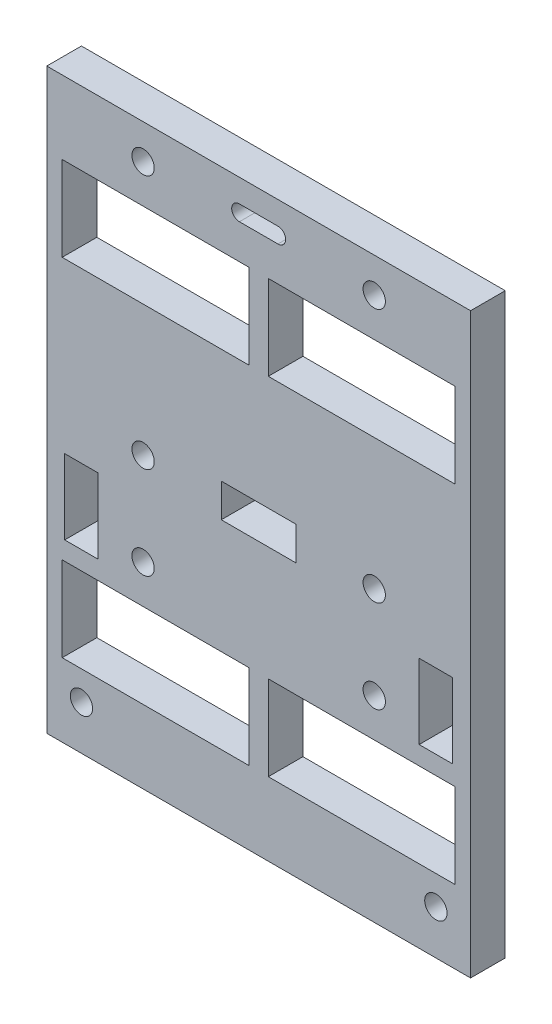
SolidWorks part; units mm, degrees
ref_plane "Front Plane" through (0, 0, 0) normal (0, 0, 1) x (1, 0, 0)
ref_plane "Top Plane" through (0, 0, 0) normal (0, 1, 0) x (1, 0, 0)
ref_plane "Right Plane" through (0, 0, 0) normal (1, 0, 0) x (0, 0, -1)
sketch "Sketch1" plane through (0, 0, 0) normal (0, 0, 1) x (1, 0, 0)
  line L0 (0, -37.5) -> (0, 37.5) construction
  line L1 (-27.5, -37.5) -> (27.5, -37.5)
  line L2 (-27.5, -37.5) -> (-27.5, 37.5)
  line L3 (-27.5, 37.5) -> (27.5, 37.5)
  line L4 (27.5, -37.5) -> (27.5, 37.5)
  line L5 (-27.5, -37.5) -> (27.5, 37.5) construction
  line L6 (-27.5, 37.5) -> (27.5, -37.5) construction
  line L7 (-27.5, 0) -> (27.5, 0) construction
  line L8 (-27.5, 22.5) -> (27.5, 22.5) construction
  line L9 (25.5, 17) -> (1.25, 28) construction
  line L10 (-25.5, 28) -> (-1.25, 28)
  line L11 (-25.5, 28) -> (-25.5, 17)
  line L12 (-25.5, 17) -> (-1.25, 17)
  line L13 (-1.25, 28) -> (-1.25, 17)
  line L14 (-25.5, 28) -> (-1.25, 17) construction
  line L15 (-25.5, 17) -> (-1.25, 28) construction
  line L16 (25.5, 28) -> (1.25, 17) construction
  line L17 (1.25, 28) -> (1.25, 17)
  line L18 (25.5, 17) -> (1.25, 17)
  line L19 (25.5, 28) -> (25.5, 17)
  line L20 (25.5, 28) -> (1.25, 28)
  line L21 (25.5, -28) -> (1.25, -17) construction
  line L22 (-25.5, -17) -> (-1.25, -28) construction
  line L23 (-25.5, -28) -> (-1.25, -17) construction
  line L24 (25.5, -17) -> (1.25, -28) construction
  line L25 (25.5, -28) -> (1.25, -28)
  line L26 (25.5, -28) -> (25.5, -17)
  line L27 (25.5, -17) -> (1.25, -17)
  line L28 (1.25, -28) -> (1.25, -17)
  line L29 (-1.25, -28) -> (-1.25, -17)
  line L30 (-25.5, -17) -> (-1.25, -17)
  line L31 (-25.5, -28) -> (-25.5, -17)
  line L32 (-25.5, -28) -> (-1.25, -28)
  point P0 (0, 0)
  point P12 (-13.375, 22.5)
  point P21 (13.375, 22.5)
  point P30 (13.375, -22.5)
  point P31 (-13.375, -22.5)
  dimension "D1" = 55
  dimension "D2" = 75
  dimension "D3" = 22.5
  dimension "D4" = 24.25
  dimension "D5" = 11
  dimension "D6" = 1.25
extrude "Boss-Extrude1" add sketch "Sketch1" along normal blind 4.5
sketch "Sketch2" plane through (0, 0, 4.5) normal (0, 0, 1) x (1, 0, 0)
  line L0 (0, -37.5) -> (0, 37.5) construction
  line L1 (-27.5, -37.5) -> (27.5, -37.5) construction
  line L2 (27.5, 37.5) -> (-27.5, 37.5) construction
  line L3 (-27.5, 0) -> (27.5, 0) construction
  line L4 (-27.5, 37.5) -> (-27.5, -37.5) construction
  line L5 (27.5, -37.5) -> (27.5, 37.5) construction
  line L6 (-15, 0) -> (15, 0) construction
  circle A0 centre (-15, 33) radius 1.45
  circle A1 centre (15, 33) radius 1.45
  circle A2 centre (15, 0) radius 1.45
  circle A3 centre (-15, 0) radius 1.45
  dimension "D1" = 2.9
  dimension "D7" = 2.9
  dimension "D8" = 2.9
  dimension "D2" = 15
  dimension "D3" = 33
  dimension "D4" = 30
  dimension "D5" = 15
  dimension "D6" = 0
extrude "screwHoles" cut sketch "Sketch2" against normal through all
sketch "Sketch3" plane through (0, 0, 4.5) normal (0, 0, 1) x (1, 0, 0)
  line L0 (-27.5, 9) -> (26.0486, 9) construction
  line L1 (-27.5, 37.5) -> (-27.5, -37.5) construction
  line L3 (0, 37.5) -> (0, -37.5) construction
  line L4 (27.5, 37.5) -> (-27.5, 37.5) construction
  line L5 (-27.5, -37.5) -> (27.5, -37.5) construction
  line L6 (18.95, 6.8) -> (9.05, 11.2) construction
  line L7 (-18.95, 11.2) -> (-9.05, 11.2)
  line L8 (-18.95, 11.2) -> (-18.95, 6.8)
  line L9 (-18.95, 6.8) -> (-9.05, 6.8)
  line L10 (-9.05, 11.2) -> (-9.05, 6.8)
  line L11 (-18.95, 11.2) -> (-9.05, 6.8) construction
  line L12 (-18.95, 6.8) -> (-9.05, 11.2) construction
  line L13 (18.95, 11.2) -> (9.05, 6.8) construction
  line L14 (9.05, 11.2) -> (9.05, 6.8)
  line L15 (18.95, 6.8) -> (9.05, 6.8)
  line L16 (18.95, 11.2) -> (18.95, 6.8)
  line L17 (18.95, 11.2) -> (9.05, 11.2)
  line L18 (-27.5, 37.5) -> (-27.5, -37.5) construction
  point P2 (-27.5, 0)
  point P12 (-14, 9)
  point P21 (14, 9)
  dimension "D1" = 9.9
  dimension "D3" = 14
  dimension "D4" = 9
extrude "BeltClamp" [suppressed] cut sketch "Sketch3" against normal through all
sketch "Sketch4" plane through (0, 0, 4.5) normal (0, 0, 1) x (1, 0, 0)
  line L0 (-27.5, 0) -> (27.5, 0) construction
  line L1 (-27.5, 37.5) -> (-27.5, -37.5) construction
  line L2 (27.5, -37.5) -> (27.5, 37.5) construction
  line L4 (-4.85, 2.175) -> (4.85, 2.175)
  line L5 (-4.85, 2.175) -> (-4.85, -2.175)
  line L6 (-4.85, -2.175) -> (4.85, -2.175)
  line L7 (4.85, 2.175) -> (4.85, -2.175)
  line L8 (-4.85, 2.175) -> (4.85, -2.175) construction
  line L9 (-4.85, -2.175) -> (4.85, 2.175) construction
  circle A0 centre (-15, 0) radius 1.45 construction
  point P6 (0, 0)
  dimension "D2" = 4.35
  dimension "D3" = 0
extrude "mountingPlateTab" cut sketch "Sketch4" against normal through all
sketch "Sketch5" plane through (0, 0, 4.5) normal (0, 0, 1) x (1, 0, 0)
  line L0 (-27.5, -9.75) -> (27.5, -9.75) construction
  line L1 (-27.5, 37.5) -> (-27.5, -37.5) construction
  line L2 (27.5, -37.5) -> (27.5, 37.5) construction
  line L4 (0, -37.5) -> (0, 37.5) construction
  line L5 (-27.5, -37.5) -> (27.5, -37.5) construction
  line L6 (27.5, 37.5) -> (-27.5, 37.5) construction
  line L7 (-20.825, -14.6) -> (-25.175, -4.9) construction
  line L8 (20.825, -4.9) -> (25.175, -4.9)
  line L9 (20.825, -4.9) -> (20.825, -14.6)
  line L10 (20.825, -14.6) -> (25.175, -14.6)
  line L11 (25.175, -4.9) -> (25.175, -14.6)
  line L12 (20.825, -4.9) -> (25.175, -14.6) construction
  line L13 (20.825, -14.6) -> (25.175, -4.9) construction
  line L14 (-20.825, -4.9) -> (-25.175, -14.6) construction
  line L15 (-25.175, -4.9) -> (-25.175, -14.6)
  line L16 (-20.825, -14.6) -> (-25.175, -14.6)
  line L17 (-20.825, -4.9) -> (-20.825, -14.6)
  line L18 (-20.825, -4.9) -> (-25.175, -4.9)
  line L19 (23, -9.75) -> (23, -37.5) construction
  line L20 (-23, -9.75) -> (-23, -37.5) construction
  circle A0 centre (23, -31.75) radius 1.45
  circle A1 centre (-23, -31.75) radius 1.45
  point P15 (23, -9.75)
  point P24 (-23, -9.75)
  dimension "D5" = 2.9
  dimension "D2" = 9.7
  dimension "D3" = 4.35
  dimension "D4" = 23
  dimension "D6" = 22
  dimension "D1" = 9.75
extrude "BraceTabs" cut sketch "Sketch5" against normal through all
sketch "Sketch6" plane through (0, 0, 4.5) normal (0, 0, 1) x (1, 0, 0)
  line L0 (-25.175, -9.75) -> (25.175, -9.75) construction
  line L1 (-25.175, -4.9) -> (-25.175, -14.6) construction
  line L2 (25.175, -14.6) -> (25.175, -4.9) construction
  line L3 (0, -2.175) -> (0, -37.5) construction
  line L4 (-4.85, -2.175) -> (4.85, -2.175) construction
  line L5 (-27.5, -37.5) -> (27.5, -37.5) construction
  line L6 (23, -14.6) -> (23, -4.9) construction
  line L7 (20.825, -14.6) -> (25.175, -14.6) construction
  line L8 (25.175, -4.9) -> (20.825, -4.9) construction
  line L9 (20.825, -4.9) -> (20.825, -14.6) construction
  line L10 (19.825, -15.6) -> (26.175, -15.6)
  line L11 (19.825, -15.6) -> (19.825, -3.9)
  line L12 (19.825, -3.9) -> (26.175, -3.9)
  line L13 (26.175, -15.6) -> (26.175, -3.9)
  line L14 (19.825, -15.6) -> (26.175, -3.9) construction
  line L15 (19.825, -3.9) -> (26.175, -15.6) construction
  line L16 (-19.825, -3.9) -> (-26.175, -15.6) construction
  line L17 (-19.825, -15.6) -> (-26.175, -3.9) construction
  line L18 (-23, -14.6) -> (-23, -4.9) construction
  line L19 (-26.175, -15.6) -> (-26.175, -3.9)
  line L20 (-19.825, -3.9) -> (-26.175, -3.9)
  line L21 (-19.825, -15.6) -> (-19.825, -3.9)
  line L22 (-19.825, -15.6) -> (-26.175, -15.6)
  circle A0 centre (23, -9.75) radius 1.45
  circle A1 centre (-23, -9.75) radius 1.45
  point P18 (23, -9.75)
  dimension "D3" = 2.9
  dimension "D1" = 1
  dimension "D2" = 1
extrude "FrontToRear1" [suppressed] add sketch "Sketch6" against normal up to surface (4.5 mm away) up to face at (-24.45, -31.75, 0)
sketch "Sketch7" plane through (0, 0, 4.5) normal (0, 0, 1) x (1, 0, 0)
  line L0 (4.85, 2.175) -> (-4.85, 2.175) construction
  line L1 (-20, -3.175) -> (20, -3.175)
  line L2 (-20, -3.175) -> (-20, 3.175)
  line L3 (-20, 3.175) -> (20, 3.175)
  line L4 (20, -3.175) -> (20, 3.175)
  line L5 (-20, -3.175) -> (20, 3.175) construction
  line L6 (-20, 3.175) -> (20, -3.175) construction
  circle A0 centre (15, 0) radius 1.45 construction
  point P0 (0, 0)
  dimension "D1" = 1
  dimension "D2" = 5
extrude "FrontToRear2" [suppressed] add sketch "Sketch7" against normal through all
sketch "Sketch8" plane through (0, 0, 4.5) normal (0, 0, 1) x (1, 0, 0)
  line L0 (-27.5, -12) -> (27.5, -12) construction
  line L1 (-27.5, 37.5) -> (-27.5, -37.5) construction
  line L2 (27.5, -37.5) -> (27.5, 37.5) construction
  line L3 (0, -37.5) -> (0, 0) construction
  line L4 (-27.5, -37.5) -> (27.5, -37.5) construction
  circle A0 centre (-15, -12) radius 1.45
  circle A1 centre (15, -12) radius 1.45
  dimension "D2" = 2.9
  dimension "D1" = 12
  dimension "D3" = 15
extrude "ExpansionScrewholes" cut sketch "Sketch8" against normal through all
sketch "Sketch12" plane through (0, 0, 4.5) normal (0, 0, 1) x (1, 0, 0)
  line L0 (0, 37.5) -> (0, 0) construction
  line L1 (27.5, 37.5) -> (-27.5, 37.5) construction
  line L2 (-2.5, 33.5) -> (2.5, 33.5) construction
  line L3 (-2.5, 34.5) -> (2.5, 34.5)
  line L4 (-2.5, 32.5) -> (2.5, 32.5)
  arc A0 (-2.5, 34.5) -> (-2.5, 32.5) centre (-2.5, 33.5) ccw
  arc A1 (2.5, 32.5) -> (2.5, 34.5) centre (2.5, 33.5) ccw
  point P7 (0, 33.5)
  dimension "D1" = 3
  dimension "D2" = 2
  dimension "D3" = 5
extrude "CableTieSlot" cut sketch "Sketch12" against normal through all
sketch "Sketch11" [suppressed] plane through (0, 0, 4.5) normal (0, 0, 1) x (1, 0, 0)
  line L0 (13.5615, -8.85) -> (27.5, -8.85) construction
  line L1 (27.5, -37.5) -> (27.5, 37.5) construction
  line L2 (0, 37.5) -> (0, -37.5) construction
  line L3 (36.5, -14.85) -> (18.5, -14.85)
  line L4 (36.5, -14.85) -> (36.5, -2.85)
  line L5 (36.5, -2.85) -> (18.5, -2.85)
  line L6 (18.5, -14.85) -> (18.5, -2.85)
  line L7 (36.5, -14.85) -> (18.5, -2.85) construction
  line L8 (36.5, -2.85) -> (18.5, -14.85) construction
  line L11 (-36.5, -2.85) -> (-18.5, -14.85) construction
  line L12 (-36.5, -14.85) -> (-18.5, -2.85) construction
  line L13 (-18.5, -14.85) -> (-18.5, -2.85)
  line L14 (-36.5, -2.85) -> (-18.5, -2.85)
  line L15 (-36.5, -14.85) -> (-36.5, -2.85)
  line L16 (-36.5, -14.85) -> (-18.5, -14.85)
  line L17 (36.5, -2.85) -> (18.5, -14.85) construction
  line L18 (20.65, -14.85) -> (25.35, -14.85) construction
  line L19 (27.5, 37.5) -> (-27.5, 37.5) construction
  line L20 (-27.5, -37.5) -> (27.5, -37.5) construction
  dimension "D1" = 9
  dimension "D2" = 12
  dimension "D3" = 0
extrude "Cut-Extrude2" [suppressed] cut sketch "Sketch11" against normal through all
sketch "Sketch10" plane through (0, 0, 4.5) normal (0, 0, 1) x (1, 0, 0)
  line L0 (4.7446, 1) -> (27.5, 1) construction
  line L1 (-4.85, 0) -> (4.85, 0) construction
  line L2 (27.5, -37.5) -> (27.5, 37.5) construction
  line L3 (0, 2.175) -> (0, -2.175) construction
  line L4 (36.5, 4) -> (18.5, 4)
  line L5 (36.5, 4) -> (36.5, -2)
  line L6 (36.5, -2) -> (18.5, -2)
  line L7 (18.5, 4) -> (18.5, -2)
  line L8 (36.5, 4) -> (18.5, -2) construction
  line L9 (36.5, -2) -> (18.5, 4) construction
  line L10 (4.85, 2.175) -> (-4.85, 2.175) construction
  line L11 (-4.85, -2.175) -> (4.85, -2.175) construction
  line L12 (-36.5, -2) -> (-18.5, 4) construction
  line L13 (-36.5, 4) -> (-18.5, -2) construction
  line L14 (-4.7446, 1) -> (-27.5, 1) construction
  line L15 (-18.5, 4) -> (-18.5, -2)
  line L16 (-36.5, -2) -> (-18.5, -2)
  line L17 (-36.5, 4) -> (-36.5, -2)
  line L18 (-36.5, 4) -> (-18.5, 4)
  line L19 (36.5, -2) -> (18.5, 4) construction
  line L20 (-4.85, 2.175) -> (-4.85, -2.175) construction
  line L21 (4.85, -2.175) -> (4.85, 2.175) construction
  dimension "D1" = 6
  dimension "D2" = 9
  dimension "D3" = 1
extrude "CableTieSlots" [suppressed] cut sketch "Sketch10" against normal through all
sketch "Sketch9" [suppressed] plane through (0, 0, 4.5) normal (0, 0, 1) x (1, 0, 0)
  line L0 (-27.5, -37.5) -> (27.5, -37.5) construction
  line L5 (-9, -42.5) -> (9, -42.5)
  line L6 (-9, -42.5) -> (-9, -34.5)
  line L7 (-7, -32.5) -> (7, -32.5)
  line L8 (9, -42.5) -> (9, -34.5)
  line L9 (-9, -42.5) -> (9, -32.5) construction
  line L10 (-9, -32.5) -> (9, -42.5) construction
  arc A0 (7, -32.5) -> (9, -34.5) centre (7, -34.5) cw
  arc A1 (-9, -34.5) -> (-7, -32.5) centre (-7, -34.5) cw
  point P9 (0, -37.5)
  dimension "D3" = 2
  dimension "D1" = 18
  dimension "D2" = 5
extrude "RearFanSlot" [suppressed] cut sketch "Sketch9" against normal through all
sketch "Sketch13" [suppressed] plane through (0, 0, 4.5) normal (0, 0, 1) x (1, 0, 0)
  line L1 (-7, -2.85) -> (7, -2.85)
  line L2 (-7, -2.85) -> (-7, -11.85)
  line L3 (-7, -11.85) -> (7, -11.85)
  line L4 (7, -2.85) -> (7, -11.85)
  line L5 (-7, -2.85) -> (7, -11.85) construction
  line L6 (-7, -11.85) -> (7, -2.85) construction
  line L9 (0, 37.5) -> (0, -7.35) construction
  line L10 (-18.5, -2.85) -> (-27.5, -2.85) construction
  line L11 (27.5, 37.5) -> (-27.5, 37.5) construction
  line L13 (-27.5, -14.85) -> (-18.5, -14.85) construction
  point P0 (0, -7.35)
  dimension "D1" = 3
  dimension "D2" = 0
  dimension "D3" = 7
extrude "Cut-Extrude3" [suppressed] cut sketch "Sketch13" against normal through all
sketch "Sketch14" [suppressed] plane through (0, 0, 4.5) normal (0, 0, 1) x (1, 0, 0)
  line L0 (25.2, -4.85) -> (20.8, -4.85) construction
  line L1 (25.2, -4.85) -> (20.8, -4.85)
  line L2 (25.2, -4.85) -> (25.2, -14.65)
  line L3 (25.2, -14.65) -> (20.8, -14.65)
  line L4 (20.8, -4.85) -> (20.8, -14.65)
  line L5 (25.2, -14.65) -> (25.2, -4.85) construction
  line L6 (0, 0) -> (0, -6.835) construction
  line L7 (-20.8, -4.85) -> (-20.8, -14.65)
  line L8 (-25.2, -14.65) -> (-20.8, -14.65)
  line L9 (-25.2, -4.85) -> (-25.2, -14.65)
  line L10 (-25.2, -4.85) -> (-20.8, -4.85)
extrude "Boss-Extrude2" [suppressed] add sketch "Sketch14" against normal through all
equation "\"X-ROD-SPACING\"=45"
equation "\"Y-ROD-SPACING\"=75"
equation "\"Z-ROD-SPACING\"=17.5"
equation "\"Y-BED-OFFSET\"=2"
equation "\"Y-BED-ROD-INSET\"=3.5"
equation "\"Y-BED-SCREW-SPACING\"=209"
equation "\"Y-BED-SCREW-CUTOUT-SLOT-HEIGHT\"=2"
equation "\"T-SLOT-NUT-FILLET-RADIUS\"=0.5"
equation "\"T-SLOT-SCREW-SHAFT-RADIUS\"=1.55"
equation "\"T-SLOT-SCREW-SHAFT-CUTOUT-LENGTH\"=11"
equation "\"T-SLOT-NUT-DEPTH\"=3.5"
equation "\"T-SLOT-NUT-WIDTH\"=2.85"
equation "\"T-SLOT-NUT-END-DISTANCE\"=8"
equation "\"ACRYLIC-THICKNESS\"=10"
equation "\"ACRYLIC-THICKNESS2\"=4.5"
equation "\"ACRYLIC-TAB-CUTOUT-SIZE\"=\"ACRYLIC-THICKNESS\"+\"ACRYLIC-TAB-TOLERANCE\"*2"
equation "\"ACRYLIC-TAB-WIDTH\"=\"ACRYLIC-THICKNESS\""
equation "\"ACRYLIC-M3-HOLE\"=2.9"
equation "\"SMOOTHROD-CAP-SCREW-DISTANCE\"=20"
equation "\"FRAME-WIDTH-INNER\"=370"
equation "\"NEMA17-HOLE-SPACING\"=31"
equation "\"NEMA17-CENTRAL-CUTOUT\"=22.5"
equation "\"Z-BRACKET-REACH\"=55"
equation "\"Z-ROD-INSET\"=13.5"
equation "\"TOP-BRACKET-SPACING\"=40"
equation "\"SMOOTHROD-X-LENGTH\"=350"
equation "\"SMOOTHROD-Y-LENGTH\"=350"
equation "\"SMOOTHROD-Z-LENGTH\"=350"
equation "\"SMOOTHROD-TIGHTENING-HEADROOM\"=.25"
equation "\"LEADSCREW-Z-LENGTH\"=300"
equation "\"SCREW-LENGTH-FRAME\"=\"ACRYLIC-THICKNESS\" + 10"
equation "\"SCREW-LENGTH-MOTOR\"=\"ACRYLIC-THICKNESS\" + 5"
equation "\"SCREW-HEAD-RADIUS\"=6"
equation "\"PRINTED-X-SMOOTHROD-DIAMETER\"=8.8"
equation "\"PRINTED-X-SMOOTHROD-CUTOUT\"=10"
equation "\"PRINTED-X-BASE-HEIGHT\"=10"
equation "\"PRINTED-LM8UU-CUTOUT-SIZE\"=15.5"
equation "\"PRINTED-LM8UU-CUTOUT-LENGTH\"=24.5"
equation "\"PRINTED-X-IDLER-HEIGHT\"=16"
equation "\"PSU-MOUNTING-WIDTH\"=95"
equation "\"PSU-MOUNTING-HEIGHT\"=177"
equation "\"Y-BELT-TO-ROD-DISTANCE\"=20"
equation "\"SPOOL-HOLDER-ROD-SPACING\"=150"
equation "\"D3@Sketch1\"=\"X-ROD-SPACING\"/2"
equation "\"D4@Sketch1\"=\"ACRYLIC-X-CARRIAGE-LM8UU-CUTOUT-WIDTH\""
equation "\"D1@Boss-Extrude1\"=\"ACRYLIC-THICKNESS2\""
equation "\"D1@Sketch2\"=\"ACRYLIC-M3-HOLE\""
equation "\"D1@Sketch3\"=\"ACRYLIC-TAB-CUTOUT-SIZE\""
equation "\"D2@Sketch3\"=\"ACRYLIC-THICKNESS2\"+\"ACRYLIC-TAB-TOLERANCE\"*2"
equation "\"ACRYLIC-X-CARRIAGE-WIDTH\"=55"
equation "\"ACRYLIC-X-CARRIAGE-HEIGHT\"=75"
equation "\"D1@Sketch1\"=\"ACRYLIC-X-CARRIAGE-WIDTH\""
equation "\"D2@Sketch1\"=\"ACRYLIC-X-CARRIAGE-HEIGHT\""
equation "\"ACRYLIC-X-CARRIAGE-CENTER-TAB-SPACING\"=14"
equation "\"D3@Sketch3\"=\"ACRYLIC-X-CARRIAGE-CENTER-TAB-SPACING\""
equation "\"SCREW-LENGTH-EXTRUDER\"=28"
equation "\"ACRYLIC-X-CARRIAGE-SCREW-SPACING-X\"=15"
equation "\"ACRYLIC-X-CARRIAGE-SCREW-SPACING-Y\"=33"
equation "\"D2@Sketch2\"=\"ACRYLIC-X-CARRIAGE-SCREW-SPACING-X\""
equation "\"D3@Sketch2\"=\"ACRYLIC-X-CARRIAGE-SCREW-SPACING-Y\""
equation "\"D1@Sketch4\"=\"ACRYLIC-TAB-WIDTH\"-\"KERF\"*4"
equation "\"D2@Sketch4\"=\"ACRYLIC-THICKNESS2\"-\"KERF\"*2"
equation "\"D2@Sketch5\"=\"ACRYLIC-TAB-WIDTH\"-\"KERF\"*4"
equation "\"D3@Sketch5\"=\"ACRYLIC-THICKNESS2\"-\"KERF\"*2"
equation "\"ACRYLIC-X-CARRIAGE-EXTRUDER-SHELF-DEPTH\"=\"ACRYLIC-X-CARRIAGE-EXTRUDER-OFFSET\" + 28"
equation "\"ACRYLIC-X-CARRIAGE-EXTRUDER-BRACE-SPACING\"=23"
equation "\"D4@Sketch5\"=\"ACRYLIC-X-CARRIAGE-EXTRUDER-BRACE-SPACING\""
equation "\"D4@Sketch2\"=\"ACRYLIC-X-CARRIAGE-SCREW-SPACING-X\"*2"
equation "\"D5@Sketch2\"=\"ACRYLIC-X-CARRIAGE-SCREW-SPACING-X\""
equation "\"D7@Sketch2\"=\"ACRYLIC-M3-HOLE\""
equation "\"D8@Sketch2\"=\"ACRYLIC-M3-HOLE\""
equation "\"ACRYLIC-X-CARRIAGE-LM8UU-CUTOUT-WIDTH\"=24.25"
equation "\"ACRYLIC-TAB-TOLERANCE\"=-.05"
equation "\"ACRYLIC-X-CARRIAGE-EXTRUDER-OFFSET\"=26"
equation "\"ACRYLIC-X-CARRIAGE-EXTRUDER-ANGLE\"=90"
equation "\"ACRYLIC-X-CARRIAGE-EXTRUDER-BRACE-TAB-OFFSET\"=20"
equation "\"ACRYLIC-X-CARRIAGE-EXTRUDER-BRACE-HEIGHT\"=35"
equation "\"ACRYLIC-X-CARRIAGE-EXTRUDER-BRACE-SCREW-SPACING\"=22"
equation "\"D5@Sketch5\"=\"ACRYLIC-M3-HOLE\""
equation "\"D3@Sketch6\"=\"ACRYLIC-M3-HOLE\""
equation "\"ACRYLIC-X-CARRIAGE-LM8UU-CUTOUT-HEIGHT\"=11.0"
equation "\"ACRYLIC-X-CARRIAGE-DUAL-WIDTH-MULTIPLIER\"=1.65"
equation "\"ACRYLIC-X-CARRIAGE-DUAL-HOTEND-SPACING\"=42"
equation "\"ACRYLIC-X-CARRIAGE-DUAL-WIDTH\"=75"
equation "\"ACRYLIC-X-CARRIAGE-DUAL-HOTEND-SEPARATION\"=36"
equation "\"ACRYLIC-X-CARRIAGE-DUAL-MOUNT-PLATE-DEPTH\"=75"
equation "\"ACRYLIC-X-CARRIAGE-DUAL-MOUNT-BRACE-WIDTH\"=33"
equation "\"ACRYLIC-X-CARRIAGE-DUAL-MOUNT-SCREW-WIDTH\"=40"
equation "\"D5@Sketch1\"=\"ACRYLIC-X-CARRIAGE-LM8UU-CUTOUT-HEIGHT\""
equation "\"D2@Sketch8\"=\"ACRYLIC-M3-HOLE\""
equation "\"D1@Sketch5\"=\"ACRYLIC-THICKNESS2\"/2 + 7.5"
equation "\"KERF\"=0.075"
equation "\"PRINTED-M3-HOLE\"=3.5"
equation "\"PRINTED-M3-NUT-AF\"=6.25"
equation "\"ACRYLIC-X-CARRIAGE-DUAL-FAN-OFFSET\"=52"
equation "\"ACRYLIC-X-CARRIAGE-DUAL-FAN-HEIGHT\"=20"
equation "\"BLOWER-FAN-WIDTH\"=15"
